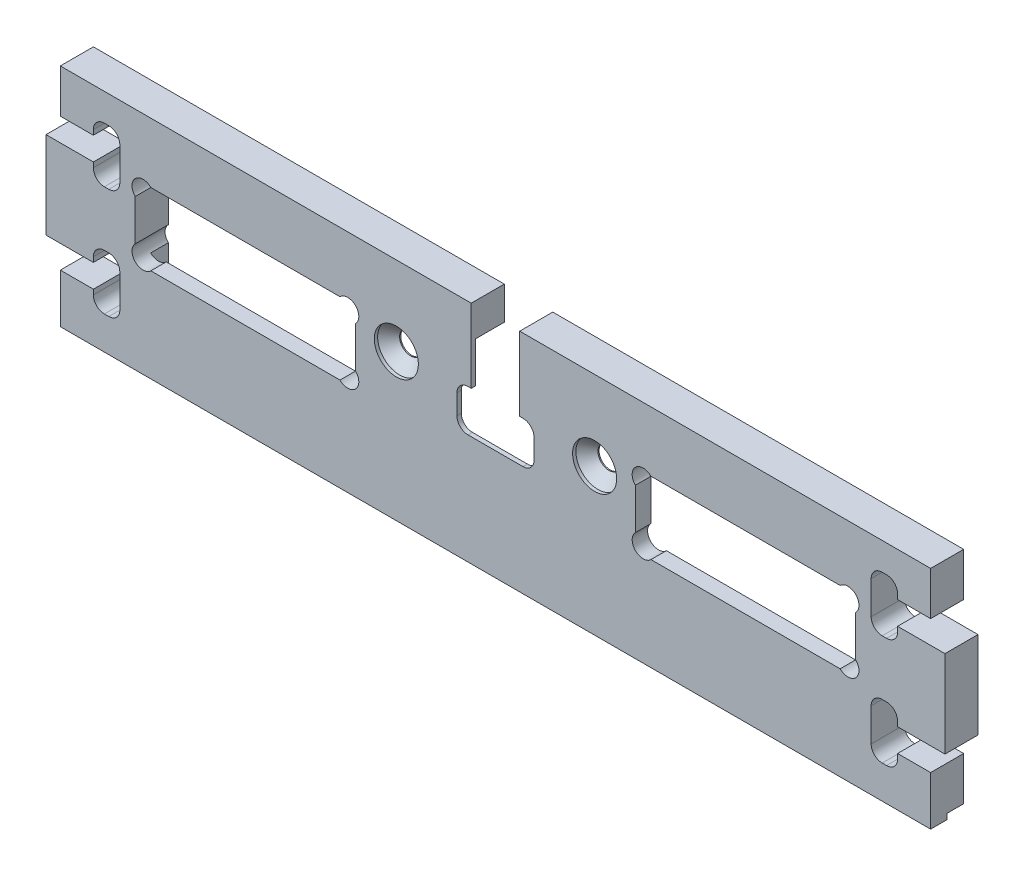
SolidWorks part; units mm, degrees
ref_plane "Front Plane" through (0, 0, 0) normal (0, 0, 1) x (1, 0, 0)
ref_plane "Top Plane" through (0, 0, 0) normal (0, 1, 0) x (1, 0, 0)
ref_plane "Right Plane" through (0, 0, 0) normal (1, 0, 0) x (0, 0, -1)
sketch "Sketch1" plane through (0, 0, 0) normal (0, 0, 1) x (1, 0, 0)
  line L0 (-39.5, 0) -> (39.5, 0) construction
  line L1 (-39.5, 10) -> (39.5, 10)
  line L2 (-39.5, 10) -> (-39.5, -10)
  line L3 (-39.5, -10) -> (39.5, -10)
  line L4 (39.5, 10) -> (39.5, -10)
  line L5 (-39.5, 10) -> (39.5, -10) construction
  line L6 (-39.5, -10) -> (39.5, 10) construction
  line L7 (0, 10) -> (0, -10) construction
  line L9 (-40.8, -3.95) -> (-39.5, -3.95)
  line L10 (-40.8, -3.95) -> (-40.8, 3.95)
  line L11 (-40.8, 3.95) -> (-39.5, 3.95)
  line L12 (-39.5, -3.95) -> (-39.5, 3.95)
  line L13 (-40.8, -3.95) -> (-39.5, 3.95) construction
  line L14 (-40.8, 3.95) -> (-39.5, -3.95) construction
  line L16 (40.8, 3.95) -> (39.5, 3.95)
  line L17 (40.8, -3.95) -> (40.8, 3.95)
  line L18 (40.8, -3.95) -> (39.5, -3.95)
  line L19 (-39.5, 5) -> (39.5, 5) construction
  line L20 (-35.3, 7.5) -> (-35.3, 2.5) construction
  line L21 (-36.5, 3.95) -> (-39.5, 3.95)
  line L22 (-36.5, 3.95) -> (-36.5, 6.05)
  line L23 (-36.5, 6.05) -> (-39.5, 6.05)
  line L24 (-39.5, 3.95) -> (-39.5, 6.05)
  line L25 (-36.5, 3.95) -> (-39.5, 6.05) construction
  line L26 (-36.5, 6.05) -> (-39.5, 3.95) construction
  line L27 (-34.1, 7.5) -> (-36.5, 7.5)
  line L28 (-34.1, 7.5) -> (-34.1, 2.5)
  line L29 (-34.1, 2.5) -> (-36.5, 2.5)
  line L30 (-36.5, 7.5) -> (-36.5, 2.5)
  line L31 (-34.1, 7.5) -> (-36.5, 2.5) construction
  line L32 (-34.1, 2.5) -> (-36.5, 7.5) construction
  line L33 (-34.1, -7.5) -> (-36.5, -7.5)
  line L34 (-34.1, -7.5) -> (-34.1, -2.5)
  line L35 (-34.1, -2.5) -> (-36.5, -2.5)
  line L36 (-36.5, -7.5) -> (-36.5, -2.5)
  line L37 (-36.5, -3.95) -> (-39.5, -3.95)
  line L38 (-36.5, -6.05) -> (-39.5, -6.05)
  line L39 (36.5, 3.95) -> (39.5, 3.95)
  line L40 (36.5, 6.05) -> (39.5, 6.05)
  line L41 (36.5, 7.5) -> (36.5, 2.5)
  line L42 (34.1, 7.5) -> (36.5, 7.5)
  line L43 (34.1, 7.5) -> (34.1, 2.5)
  line L44 (34.1, 2.5) -> (36.5, 2.5)
  line L45 (34.1, -2.5) -> (36.5, -2.5)
  line L46 (34.1, -7.5) -> (34.1, -2.5)
  line L47 (34.1, -7.5) -> (36.5, -7.5)
  line L48 (36.5, -7.5) -> (36.5, -2.5)
  line L49 (36.5, -6.05) -> (39.5, -6.05)
  line L50 (36.5, -3.95) -> (39.5, -3.95)
  point P0 (0, 0)
  point P10 (-40.15, 0)
  point P15 (-38, 5)
  point P35 (-35.3, 5)
  dimension "D1" = 79
  dimension "D2" = 20
  dimension "D4" = 1.3
  dimension "D7" = 5
  dimension "D8" = 2.1
  dimension "D9" = 3
  dimension "D10" = 2.4
  dimension "D11" = 5
extrude "Base shape" add sketch "Sketch1" along normal blind 3 contours L4 L1 L2 L3 | L9 L2 L11 L10 | L16 L4 L18 L17 region at (0, 0, 0) region at (-40.15, 0, 0) region at (40.15, 0, 0)
sketch "Sketch4" plane through (0, -10, 0) normal (0, -1, 0) x (1, 0, 0)
  line L0 (39.5, 3) -> (39.5, 0) construction
  line L1 (-39.5, 3) -> (39.5, 3)
  line L2 (-39.5, 3) -> (-39.5, 1.5)
  line L3 (-39.5, 1.5) -> (39.5, 1.5)
  line L4 (39.5, 3) -> (39.5, 1.5)
extrude "Floor lip" add sketch "Sketch4" along normal blind 0.5
sketch "Sketch6" plane through (0, 0, 0) normal (0, 0, -1) x (-1, 0, 0)
  line L0 (0, 0) -> (0, -10) construction
  line L1 (39.5, -10) -> (-39.5, -10) construction
  line L2 (-4, -10) -> (4, -10) construction
  line L3 (39.5, -10) -> (-39.5, -10) construction
  line L4 (-4, -9) -> (4, -9)
  line L5 (-4, -11) -> (4, -11)
  arc A0 (-4, -9) -> (-4, -11) centre (-4, -10) ccw
  arc A1 (4, -11) -> (4, -9) centre (4, -10) ccw
  point P9 (0, -10)
  dimension "D1" = 2
  dimension "D2" = 8
extrude "Nail cutout" cut sketch "Sketch6" against normal up to surface (1.5 mm away) up to face at (0, -10.25, 1.5)
sketch "Sketch3" plane through (-40.8, 0, 0) normal (-1, 0, 0) x (0, 0, 1)
  line L0 (0, 6.05) -> (3, 3.95) construction
  line L1 (0, 6.05) -> (3, 6.05)
  line L2 (0, 6.05) -> (0, 3.95)
  line L3 (0, 3.95) -> (3, 3.95)
  line L4 (3, 6.05) -> (3, 3.95)
  line L5 (0, -3.95) -> (3, -6.05) construction
  line L6 (0, -3.95) -> (3, -3.95)
  line L7 (0, -3.95) -> (0, -6.05)
  line L8 (0, -6.05) -> (3, -6.05)
  line L9 (3, -3.95) -> (3, -6.05)
  point P6 (1.5, 5)
  point P13 (1.5, -5)
ref_axis "Tap axis top" through (-53.7846, 5, 1.5) along (1, 0, 0)
ref_axis "Tap axis bottom" through (-54.2844, -5, 1.5) along (1, 0, 0)
fillet "Mill fillets" radius 1 16 edges at (36.5, -7.5, 1.5) (36.5, 2.5, 1.5) (34.1, 2.5, 1.5) (34.1, -7.5, 1.5) (36.5, -2.5, 1.5) (36.5, 7.5, 1.5) (34.1, -2.5, 1.5) (34.1, 7.5, 1.5) (-36.5, -2.5, 1.5) (-34.1, -2.5, 1.5) (-34.1, -7.5, 1.5) (-36.5, -7.5, 1.5) (-36.5, 2.5, 1.5) (-34.1, 2.5, 1.5) (-34.1, 7.5, 1.5) (-36.5, 7.5, 1.5)
sketch "Sketch8" [suppressed] plane through (0, 0, 3) normal (0, 0, 1) x (1, 0, 0)
  line L0 (-40.8, 0) -> (40.8, 0) construction
  line L1 (-40.8, -3.95) -> (-40.8, 3.95) construction
  line L2 (40.8, -3.95) -> (40.8, 3.95) construction
  line L4 (-24.5, 5.15) -> (24.5, 5.15)
  line L5 (-25.5, 4.15) -> (-25.5, -4.15)
  line L6 (-24.5, -5.15) -> (24.5, -5.15)
  line L7 (25.5, 4.15) -> (25.5, -4.15)
  line L8 (-25.5, 5.15) -> (25.5, -5.15) construction
  line L9 (-25.5, -5.15) -> (25.5, 5.15) construction
  arc A0 (24.5, -5.15) -> (25.5, -4.15) centre (24.5, -4.15) ccw
  arc A1 (24.5, 5.15) -> (25.5, 4.15) centre (24.5, 4.15) cw
  arc A2 (-25.5, -4.15) -> (-24.5, -5.15) centre (-24.5, -4.15) ccw
  arc A3 (-24.5, 5.15) -> (-25.5, 4.15) centre (-24.5, 4.15) ccw
  point P6 (0, 0)
  dimension "D3" = 1
  dimension "D1" = 51
  dimension "D2" = 10.3
extrude "Led strip pocket" [suppressed] cut sketch "Sketch8" against normal offset from surface (2.5 mm away) 0.5 up to face at (0, -0.6712, 0)
sketch "Sketch9" [suppressed] plane through (0, 0, 0.5) normal (0, 0, 1) x (1, 0, 0)
  line L0 (-19.5, 5.15) -> (-19.5, -5.15)
  line L1 (0, 5.15) -> (0, -5.15) construction
  line L2 (19.5, 5.15) -> (19.5, -5.15)
  line L3 (-25.5, -2.978) -> (25.5, -2.978) construction
  line L4 (25.5, -4.15) -> (25.5, 4.15)
  line L5 (24.5, 5.15) -> (-24.5, 5.15)
  line L6 (-25.5, 4.15) -> (-25.5, -4.15)
  line L7 (-24.5, -5.15) -> (24.5, -5.15)
  line L8 (25.5, -4.15) -> (25.5, 4.15)
  line L9 (24.5, 5.15) -> (-24.5, 5.15)
  line L10 (-25.5, 4.15) -> (-25.5, -4.15)
  line L11 (-24.5, -5.15) -> (24.5, -5.15)
  circle A0 centre (-12.7, -2.978) radius 1
  circle A1 centre (12.7, -2.978) radius 1
  arc A4 (24.5, -5.15) -> (25.5, -4.15) centre (24.5, -4.15) ccw
  arc A5 (25.5, 4.15) -> (24.5, 5.15) centre (24.5, 4.15) ccw
  arc A6 (-24.5, 5.15) -> (-25.5, 4.15) centre (-24.5, 4.15) ccw
  arc A7 (-25.5, -4.15) -> (-24.5, -5.15) centre (-24.5, -4.15) ccw
  arc A8 (24.5, -5.15) -> (25.5, -4.15) centre (24.5, -4.15) ccw
  arc A9 (25.5, 4.15) -> (24.5, 5.15) centre (24.5, 4.15) ccw
  arc A10 (-24.5, 5.15) -> (-25.5, 4.15) centre (-24.5, 4.15) ccw
  arc A11 (-25.5, -4.15) -> (-24.5, -5.15) centre (-24.5, -4.15) ccw
  arc M13 (24.5, -5.15) -> (25.5, -4.15) centre (24.5, -4.15) ccw
  line M14 (25.5, -4.15) -> (25.5, 4.15)
  arc M15 (25.5, 4.15) -> (24.5, 5.15) centre (24.5, 4.15) ccw
  line M16 (24.5, 5.15) -> (-24.5, 5.15)
  arc M17 (-24.5, 5.15) -> (-25.5, 4.15) centre (-24.5, 4.15) ccw
  line M18 (-25.5, 4.15) -> (-25.5, -4.15)
  arc M19 (-25.5, -4.15) -> (-24.5, -5.15) centre (-24.5, -4.15) ccw
  line M20 (-24.5, -5.15) -> (24.5, -5.15)
  dimension "D4" = 2
  dimension "D2" = 6
  dimension "D3" = 8.128
  dimension "D5" = 25.4
  dimension "D1" = 0
extrude "Led strip cuts" [suppressed] cut sketch "Sketch9" against normal up to next contours L0 M16 M17 M18 M19 M20 | L2 M16 M20 M13 M14 M15 | A0 | A1
fillet "Led strip cut fillets" [suppressed] radius 1
sketch "Sketch13" plane through (0, 0, 0) normal (0, 0, -1) x (-1, 0, 0)
  line L0 (0, 15.8648) -> (0, -21.9195) construction
  line L2 (-4.2, -6.3) -> (4.2, -6.3)
  line L3 (-5.2, -5.3) -> (-5.2, 6)
  line L4 (-4.2, 7) -> (4.2, 7)
  line L5 (5.2, -5.3) -> (5.2, 6)
  line L6 (-5.2, -6.3) -> (5.2, 7) construction
  line L7 (-5.2, 7) -> (5.2, -6.3) construction
  line L10 (39.5, 10) -> (-39.5, 10) construction
  arc A0 (-4.2, -6.3) -> (-5.2, -5.3) centre (-4.2, -5.3) cw
  arc A1 (4.2, -6.3) -> (5.2, -5.3) centre (4.2, -5.3) ccw
  arc A4 (5.2, 6) -> (4.2, 7) centre (4.2, 6) ccw
  arc A5 (-5.2, 6) -> (-4.2, 7) centre (-4.2, 6) cw
  point P1 (0, 0.35)
  dimension "D4" = 1
  dimension "D5" = 1
  dimension "D1" = 10.4
  dimension "D2" = 13.3
  dimension "D3" = 3
extrude "Bumper mount inner cut" cut sketch "Sketch13" against normal offset from surface (2.6 mm away) 0.4 up to face at (0, -0.0192, 3)
sketch "Sketch14" plane through (0, 0, 0) normal (0, 0, -1) x (-1, 0, 0)
  line L1 (0, 12.9528) -> (0, -14.0841) construction
  line L2 (4.2, 7) -> (-4.2, 7) construction
  line L3 (-4.2, -6.3) -> (4.2, -6.3) construction
  line L4 (-11.7, 7) -> (11.7, 7)
  line L5 (-12.7, 6) -> (-12.7, -5.3)
  line L6 (-11.7, -6.3) -> (11.7, -6.3)
  line L7 (12.7, 6) -> (12.7, -5.3)
  line L8 (-12.7, 7) -> (12.7, -6.3) construction
  line L9 (-12.7, -6.3) -> (12.7, 7) construction
  arc A1 (11.7, -6.3) -> (12.7, -5.3) centre (11.7, -5.3) ccw
  arc A2 (-12.7, -5.3) -> (-11.7, -6.3) centre (-11.7, -5.3) ccw
  arc A3 (11.7, 7) -> (12.7, 6) centre (11.7, 6) cw
  arc A4 (-12.7, 6) -> (-11.7, 7) centre (-11.7, 6) cw
  point P6 (0, 0.35)
  dimension "D2" = 1
  dimension "D3" = 1
  dimension "D1" = 25.4
extrude "Bumper mount outer cut" cut sketch "Sketch14" against normal blind 1.6
sketch "Sketch15" plane through (0, 0, 1.6) normal (0, 0, -1) x (-1, 0, 0)
  line L0 (-12.7, 2.8) -> (12.7, 2.8) construction
  line L3 (0, 16.4744) -> (0, -20.0474) construction
  line L7 (-12.7, 6) -> (-12.7, -5.3) construction
  line L8 (12.7, -5.3) -> (12.7, 6) construction
  line L11 (-4.2, 7) -> (-11.7, 7) construction
  circle A0 centre (-9, 2.8) radius 1
  circle A1 centre (9, 2.8) radius 1
  dimension "D1" = 18
  dimension "D2" = 2
  dimension "D3" = 4.2
extrude "Bumper mount screw holes" cut sketch "Sketch15" against normal up to next
sketch "Sketch16" plane through (0, 0, 2.6) normal (0, 0, -1) x (-1, 0, 0)
  line L0 (-5.2, 1.4) -> (5.2, 1.4) construction
  line L3 (0, 7) -> (0, -4.2) construction
  line L4 (-2.5, 3.3) -> (2.5, 3.3)
  line L5 (-3.5, 2.3) -> (-3.5, 0.5)
  line L6 (-2.5, -0.5) -> (2.5, -0.5)
  line L7 (3.5, 2.3) -> (3.5, 0.5)
  line L8 (-3.5, 3.3) -> (3.5, -0.5) construction
  line L9 (-3.5, -0.5) -> (3.5, 3.3) construction
  line L11 (-5.2, 6) -> (-5.2, -5.3) construction
  line L13 (4.2, 7) -> (-4.2, 7) construction
  arc A0 (2.5, -0.5) -> (3.5, 0.5) centre (2.5, 0.5) ccw
  arc A1 (-3.5, 0.5) -> (-2.5, -0.5) centre (-2.5, 0.5) ccw
  arc A2 (-2.5, 3.3) -> (-3.5, 2.3) centre (-2.5, 2.3) ccw
  arc A3 (2.5, 3.3) -> (3.5, 2.3) centre (2.5, 2.3) cw
  point P6 (0, 1.4)
  dimension "D3" = 1
  dimension "D1" = 7
  dimension "D2" = 3.8
  dimension "D4" = 11.2
extrude "Bumper body cut" cut sketch "Sketch16" against normal up to next
hole_wizard "Bumper screw countersunks" positions "Sketch17" profile "Sketch18" countersink size "M2" standard "ANSI Metric" end condition through all
sketch "Sketch17" plane through (0, 0, 3) normal (0, 0, 1) x (1, 0, 0)
  point P0 (9, 2.8)
  point P3 (-9, 2.8)
sketch "Sketch18" plane through (9, 2.8, 3) normal (1, 0, 0) x (0, -1, 0)
  line L0 (0, 0) -> (0, 3)
  line L1 (0, 3) -> (1, 3)
  line L2 (1, 3) -> (1, 1.3)
  line L3 (1, 1.3) -> (2, 0.3)
  line L4 (2, 0.3) -> (2, 0)
  line L6 (2, 0) -> (0, 0)
  line L7 (-1, 1.3) -> (-2, 0.3) construction
  line L11 (0, -6.35) -> (0, 107.95) construction
  dimension "Thru Hole Dia." = 2
  dimension "Thru Hole Depth" = 3
  dimension "C'Sink Dia." = 4
  dimension "C'Sink Angle" = 90
  dimension "Head Clearance" = 0.3
sketch "Sketch19" plane through (0, 0, 0) normal (0, 0, -1) x (-1, 0, 0)
  line L0 (0, 15.6498) -> (0, -12.9575) construction
  line L1 (39.5, 10) -> (-39.5, 10) construction
  line L2 (-2.2, 3.3) -> (2.2, 3.3)
  line L3 (-2.2, 3.3) -> (-2.2, 10)
  line L4 (-2.2, 10) -> (2.2, 10)
  line L5 (2.2, 3.3) -> (2.2, 10)
  line L6 (-2.2, 3.3) -> (2.2, 10) construction
  line L7 (-2.2, 10) -> (2.2, 3.3) construction
  line L8 (2.5, 3.3) -> (-2.5, 3.3) construction
  point P1 (0, 6.65)
  dimension "D1" = 4.4
extrude "Bumper insertion cut" cut sketch "Sketch19" against normal up to next
sketch "Sketch20" plane through (0, 0, 0) normal (0, 0, -1) x (-1, 0, 0)
  line L0 (-12.7, 6) -> (-12.7, -5.3) construction
  line L1 (-12.7, 4.55) -> (-32.7, 4.55)
  line L2 (-12.7, 4.55) -> (-12.7, -2)
  line L3 (-12.7, -2) -> (-32.7, -2)
  line L4 (-32.7, 4.55) -> (-32.7, -2)
  line L5 (-2.2, 10) -> (-39.5, 10) construction
  line L6 (-12.7, 4.55) -> (-19.25, -2) construction
  line L7 (-22.7, 4.55) -> (-22.7, -2) construction
  line L8 (-32.7, 1.275) -> (-12.7, 1.275) construction
  line L9 (0, 16.176) -> (0, -15.99) construction
  line L10 (12.7, 4.55) -> (12.7, -2)
  line L11 (12.7, -2) -> (32.7, -2)
  line L12 (32.7, 4.55) -> (32.7, -2)
  line L13 (12.7, 4.55) -> (32.7, 4.55)
  circle A0 centre (-13.4071, 3.8429) radius 1
  circle A1 centre (-31.9929, 3.8429) radius 1
  circle A2 centre (-13.4071, -1.2929) radius 1
  circle A3 centre (-31.9929, -1.2929) radius 1
  circle A4 centre (13.4071, 3.8429) radius 1
  circle A5 centre (13.4071, -1.2929) radius 1
  circle A6 centre (31.9929, -1.2929) radius 1
  circle A7 centre (31.9929, 3.8429) radius 1
  dimension "D5" = 2
  dimension "D1" = 20
  dimension "D2" = 5.45
  dimension "D3" = 6.55
  dimension "D4" = 45
extrude "Bumper switches cut" cut sketch "Sketch20" against normal up to next contours L1 L4 L3 L2 | A1 | A3 | A0 | A2 | L13 L12 L11 L10 | A4 | A5 | A6 | A7
sketch "Sketch21" plane through (0, 0, 0) normal (0, 0, -1) x (-1, 0, 0)
  line L0 (-14.1142, -2) -> (-31.2858, -2) construction
  line L1 (-32.7, -2) -> (-12.7, -2)
  line L2 (-32.7, -2) -> (-32.7, -6.3)
  line L3 (-32.7, -6.3) -> (-12.7, -6.3)
  line L4 (-12.7, -2) -> (-12.7, -6.3)
  line L5 (-12.7, -2) -> (-12.7, -5.3) construction
  line L6 (-11.7, -6.3) -> (-4.2, -6.3) construction
  line L7 (-32.7, 3.1358) -> (-32.7, -0.5858) construction
  line L8 (-12.7, -6.3) -> (-11.7, -6.3)
  line L9 (-32.7, -6.3) -> (-28.4, -2) construction
  line L10 (0, 14.2019) -> (0, -15.3745) construction
  line L11 (12.7, -6.3) -> (11.7, -6.3)
  line L12 (12.7, -2) -> (12.7, -6.3)
  line L13 (32.7, -2) -> (12.7, -2)
  line L14 (32.7, -2) -> (32.7, -6.3)
  line L15 (32.7, -6.3) -> (12.7, -6.3)
  arc A0 (-12.7, -5.3) -> (-11.7, -6.3) centre (-11.7, -5.3) ccw construction
  arc A1 (-12.7, -5.3) -> (-11.7, -6.3) centre (-11.7, -5.3) ccw
  circle A2 centre (-31.9929, -5.5929) radius 1
  arc A3 (-32.7, -0.5858) -> (-31.2858, -2) centre (-31.9929, -1.2929) ccw construction
  circle A4 centre (31.9929, -5.5929) radius 1
  arc A5 (12.7, -5.3) -> (11.7, -6.3) centre (11.7, -5.3) cw
  dimension "D1" = 45
extrude "Bumper switch mounts cut" cut sketch "Sketch21" against normal up to surface (1.6 mm away) contours A1 L4 L8 | L12 A5 L11 | L4 L1 L2 L3 | A2 | L12 L13 L14 L15 | A4 region at (12.4766, -6.0766, 0) region at (-12.4766, -6.0766, 0) up to face at (-8, 2.8, 1.6)
sketch "Outer coordinate system sketch" plane through (0, 0, 3) normal (0, 0, 1) x (1, 0, 0)
  line L0 (-35.3, 7.5) -> (-35.3, 2.5) construction
  line L1 (-35.1, 7.5) -> (-35.5, 7.5) construction
  line L2 (-40.8, 3.95) -> (-40.8, 10) construction
  line L3 (-40.8, 10) -> (-39.5, 10) construction
  line L4 (-35.1, 2.5) -> (-35.5, 2.5) construction
  line L5 (0, 15.526) -> (0, -17.3739) construction
  line L6 (-51.2617, 0) -> (56.0692, 0) construction
  circle A0 centre (-35.3, 6.5) radius 1
  point P16 (-35.3, 6.5)
  point P20 (0, 0)
  point P22 (35.3, 6.5)
  point P23 (0, 0)
  point P24 (-35.3, -6.5)
  point P25 (35.3, -6.5)
  dimension "D1" = 2
sketch "Inner coordinate system sketch" plane through (0, 0, 0) normal (0, 0, 1) x (1, 0, 0)
  line L0 (-40.8, -3.95) -> (-40.8, -10) construction
  line L1 (-40.8, -10) -> (-39.5, -10) construction
  line L3 (0, 19.9465) -> (0, -19.5427) construction
  line L4 (53.9633, 0) -> (-51.6097, 0) construction
  point P1 (0, 0)
  point P4 (0, 0)
  point P5 (0, 0)
  point P6 (0, 0)
  point P9 (0, 0)
  point P11 (0, 0)
  point P15 (-39.5, -10)
sketch "Deep inner pocket mill sketch" plane through (0, 0, 2.6) normal (0, 0, -1) x (-1, 0, 0)
  line L0 (-4.2, 7) -> (4.2, 7)
  line L12 (4.2, 7) -> (2.2, 7)
  line L13 (2.2, 7) -> (2.2, 3.3)
  line L14 (2.2, 3.3) -> (2.5, 3.3)
  line L15 (3.5, 2.3) -> (3.5, 0.5)
  line L16 (2.5, -0.5) -> (-2.5, -0.5)
  line L17 (-3.5, 0.5) -> (-3.5, 2.3)
  line L18 (-2.5, 3.3) -> (-2.2, 3.3)
  line L19 (-2.2, 3.3) -> (-2.2, 7)
  line L20 (-2.2, 7) -> (-4.2, 7)
  line L21 (-5.2, 6) -> (-5.2, -5.3)
  line L22 (-4.2, -6.3) -> (4.2, -6.3)
  line L23 (5.2, -5.3) -> (5.2, 6)
  line L33 (-5.2, 6) -> (-5.2, -5.3)
  line L34 (-4.2, -6.3) -> (4.2, -6.3)
  line L35 (5.2, -5.3) -> (5.2, 6)
  arc A8 (3.5, 2.3) -> (2.5, 3.3) centre (2.5, 2.3) ccw
  arc A9 (2.5, -0.5) -> (3.5, 0.5) centre (2.5, 0.5) ccw
  arc A10 (-3.5, 0.5) -> (-2.5, -0.5) centre (-2.5, 0.5) ccw
  arc A11 (-2.5, 3.3) -> (-3.5, 2.3) centre (-2.5, 2.3) ccw
  arc A12 (-4.2, 7) -> (-5.2, 6) centre (-4.2, 6) ccw
  arc A13 (-5.2, -5.3) -> (-4.2, -6.3) centre (-4.2, -5.3) ccw
  arc A14 (4.2, -6.3) -> (5.2, -5.3) centre (4.2, -5.3) ccw
  arc A15 (5.2, 6) -> (4.2, 7) centre (4.2, 6) ccw
  arc A20 (-4.2, 7) -> (-5.2, 6) centre (-4.2, 6) ccw
  arc A21 (-5.2, -5.3) -> (-4.2, -6.3) centre (-4.2, -5.3) ccw
  arc A22 (4.2, -6.3) -> (5.2, -5.3) centre (4.2, -5.3) ccw
  arc A23 (5.2, 6) -> (4.2, 7) centre (4.2, 6) ccw
  dimension "D1" = 0
sketch "Shallow inner pocket mill sketch" plane through (0, 0, 1.6) normal (0, 0, -1) x (-1, 0, 0)
  line L2 (12.7, 4.55) -> (12.7, 6) construction
  line L7 (-12.7, 6) -> (-12.7, 4.55) construction
  line L16 (12.7, 4.55) -> (12.7, 6)
  line L21 (-12.7, 6) -> (-12.7, 4.55)
  line L42 (-32.7, -1) -> (-13.7, -1)
  line L43 (-12.7, 3.1358) -> (-12.7, -0.5858) construction
  line L47 (0, 16.1275) -> (0, -14.7685) construction
  line L53 (-31.2858, -6.3) -> (31.2858, -6.3)
  line L54 (-11.7, 7) -> (11.7, 7)
  line L55 (-12.7, 4.55) -> (-13.7, 4.55)
  line L56 (-13.7, 4.55) -> (-13.7, -1)
  line L58 (-22.7, -2) -> (-22.7, -1) construction
  line L59 (-31.2858, -2) -> (-14.1142, -2) construction
  line L60 (-12.7, 1.275) -> (-13.7, 1.275) construction
  line L61 (-32.7, -1) -> (-32.7, -4.8858)
  line L62 (12.7, 4.55) -> (13.7, 4.55)
  line L63 (13.7, 4.55) -> (13.7, -1)
  line L64 (32.7, -1) -> (13.7, -1)
  line L65 (32.7, -1) -> (32.7, -4.8858)
  arc A2 (12.7, 6) -> (11.7, 7) centre (11.7, 6) ccw construction
  arc A5 (31.2858, -6.3) -> (32.7, -4.8858) centre (31.9929, -5.5929) ccw construction
  arc A10 (-32.7, -4.8858) -> (-31.2858, -6.3) centre (-31.9929, -5.5929) ccw construction
  arc A13 (-11.7, 7) -> (-12.7, 6) centre (-11.7, 6) ccw construction
  arc A16 (12.7, 6) -> (11.7, 7) centre (11.7, 6) ccw
  arc A19 (31.2858, -6.3) -> (32.7, -4.8858) centre (31.9929, -5.5929) ccw
  arc A24 (-32.7, -4.8858) -> (-31.2858, -6.3) centre (-31.9929, -5.5929) ccw
  arc A27 (-11.7, 7) -> (-12.7, 6) centre (-11.7, 6) ccw
  dimension "D1" = 1
